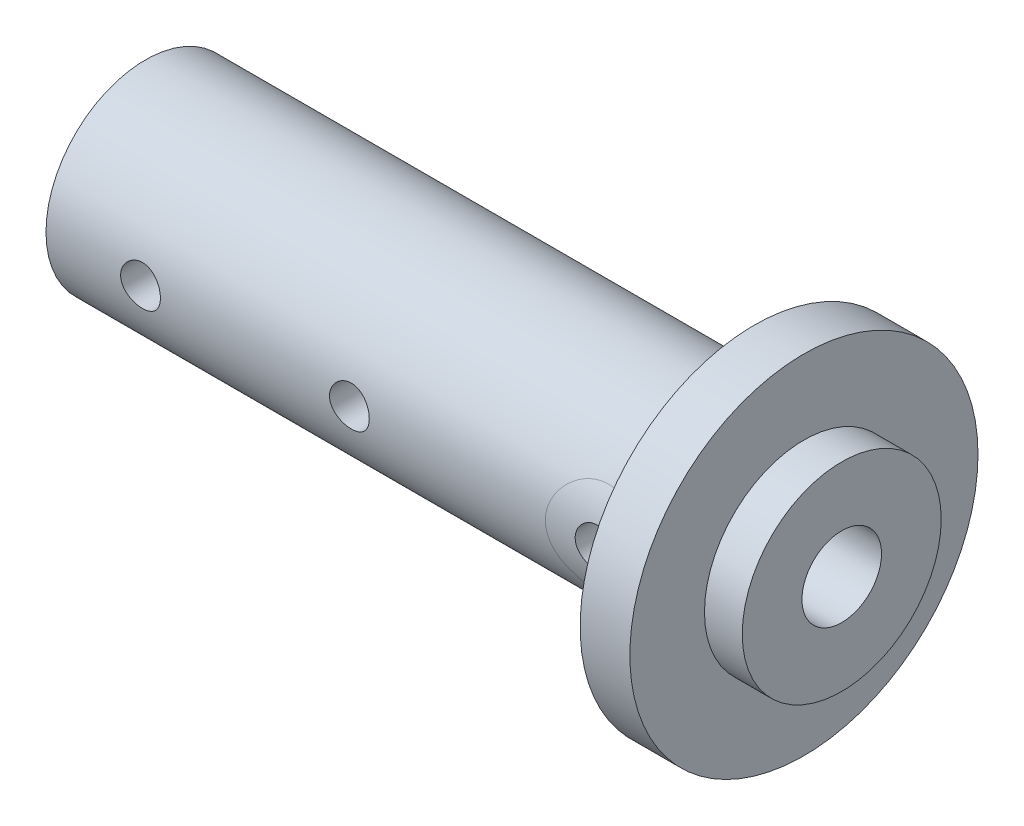
SolidWorks part; units mm, degrees
material "1.0570 (S355J2G3)"
ref_plane "Front Plane" through (0, 0, 0) normal (0, 0, 1) x (1, 0, 0)
ref_plane "Top Plane" through (0, 0, 0) normal (0, 1, 0) x (1, 0, 0)
ref_plane "Right Plane" through (0, 0, 0) normal (1, 0, 0) x (0, 0, -1)
sketch "Sketch1" plane through (0, 0, 0) normal (0, 1, 0) x (1, 0, 0)
  line L1 (-3.8, 17.5) -> (-8.8, 17.5)
  line L2 (-8.8, 17.5) -> (-8.8, 10)
  line L3 (-8.8, 10) -> (-70, 10)
  line L4 (-70, 10) -> (-70, 0)
  line L5 (-70, 0) -> (0, 0) construction
  line L6 (0, 0) -> (-70, 0)
  line L7 (-3.8, 17.5) -> (-3.8, 10)
  line L8 (-3.8, 10) -> (0, 10)
  line L9 (0, 10) -> (0, 4)
  line L10 (0, 4) -> (-19, 4)
  line L11 (-19, 4) -> (-19, 0)
  dimension "D1" = 5
  dimension "D2" = 17.5
  dimension "D3" = 10
  dimension "D4" = 70
  dimension "D5" = 3.8
  dimension "D6" = 4
  dimension "D7" = 19
revolve "Revolve2" add sketch "Sketch1" angle 360 about L6 region at (-36.3027, 0, -5.8407)
sketch "Sketch5" plane through (0, 0, 0) normal (0, 0, 1) x (1, 0, 0)
  line L0 (-8.8, 17.5) -> (-8.8, -17.5) construction
  circle A0 centre (-39.5, 0) radius 2
  circle A1 centre (-60.5, 0) radius 2
  circle A2 centre (-39.5, 0) radius 2 construction
  circle A3 centre (-60.5, 0) radius 2 construction
  circle A4 centre (-14.8, 0) radius 2
  dimension "D1" = 6
extrude "Cut-Extrude2" cut sketch "Sketch5" against normal through all both and the other way through all
sketch "Sketch6" plane through (0, 0, 0) normal (0, 0, 1) x (1, 0, 0)
  circle A0 centre (-14.8, 0) radius 5
  dimension "D1" = 10
split line "Split Line1"
